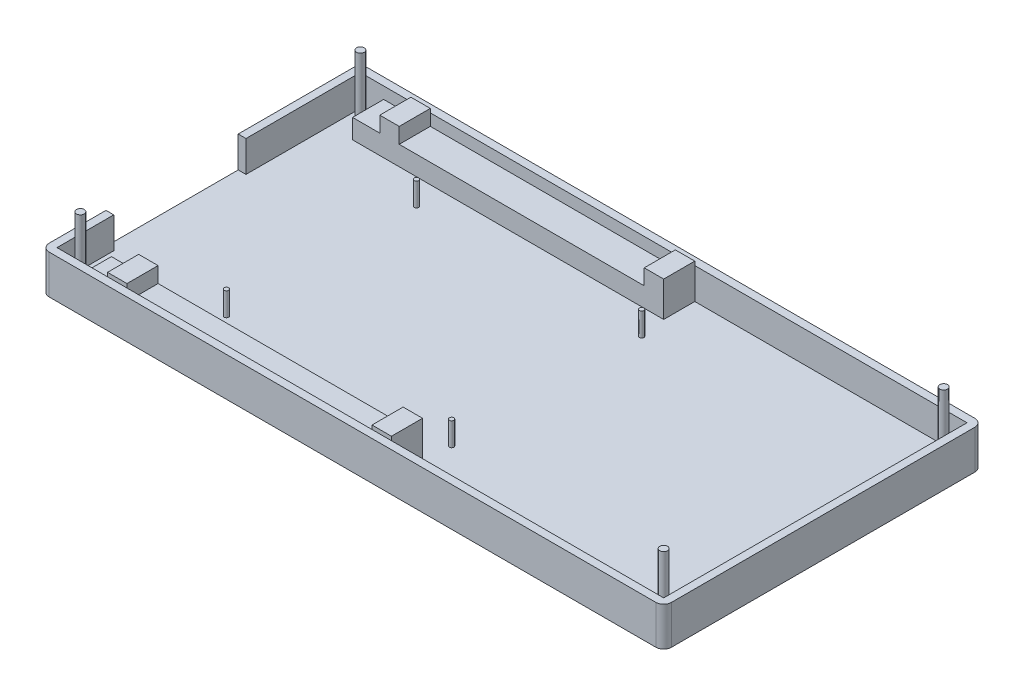
SolidWorks part; units mm, degrees
ref_plane "Front Plane" through (0, 0, 0) normal (0, 0, 1) x (1, 0, 0)
ref_plane "Top Plane" through (0, 0, 0) normal (0, 1, 0) x (1, 0, 0)
ref_plane "Right Plane" through (0, 0, 0) normal (1, 0, 0) x (0, 0, -1)
sketch "Sketch1" plane through (0, 0, 0) normal (0, 1, 0) x (1, 0, 0)
  line L1 (-80, -41) -> (80, -41)
  line L2 (-80, -41) -> (-80, 41)
  line L3 (-80, 41) -> (80, 41)
  line L4 (80, -41) -> (80, 41)
  line L5 (-80, -41) -> (80, 41) construction
  line L6 (-80, 41) -> (80, -41) construction
  point P0 (0, 0)
  dimension "D1" = 160
  dimension "D2" = 82
extrude "Boss-Extrude1" add sketch "Sketch1" along normal blind 10 contours L1 L4 L3 L2
shell "Shell1" thickness 2 removed face at (0, 10, 0)
sketch "Sketch2" plane through (0, 2, 0) normal (0, 1, 0) x (1, 0, 0)
  line L0 (-78, 39) -> (78, 39) construction
  line L1 (-78, -39) -> (-78, 39) construction
  line L2 (0, 39) -> (0, -41) construction
  line L3 (-78, 39) -> (78, 39) construction
  line L4 (-80, -41) -> (80, -41) construction
  line L5 (-80, 0) -> (80, 0) construction
  line L6 (-80, -41) -> (-80, 41) construction
  line L7 (80, -41) -> (80, 41) construction
  circle A0 centre (-75, 36) radius 1
  circle A1 centre (75, 36) radius 1
  circle A2 centre (75, -36) radius 1
  circle A3 centre (-75, -36) radius 1
  dimension "D1" = 3
  dimension "D2" = 3
  dimension "D3" = 2
extrude "Boss-Extrude2" add sketch "Sketch2" along normal blind 16 contours A0 | A3 | A2 | A1
fillet "Fillet1" radius 2 1 edges at (-80, 5, 41)
fillet "Fillet2" radius 2 1 edges at (-80, 5, -41)
fillet "Fillet3" radius 2 1 edges at (80, 5, -41)
fillet "Fillet4" radius 2 1 edges at (80, 5, 41)
sketch "Sketch7" plane through (0, 2, 0) normal (0, 1, 0) x (1, 0, 0)
  line L0 (-49, 24.45) -> (-49, -24.43)
  line L1 (-78, 39) -> (78, 39) construction
  line L2 (-20.05, 24.45) -> (-20.05, -24.43) construction
  line L3 (-49, 0.01) -> (-52.9634, 0.01) construction
  line L4 (-49, 24.45) -> (8.9, 24.45)
  line L5 (8.9, 24.45) -> (8.9, -24.43)
  line L6 (8.9, -24.43) -> (-49, -24.43)
  line L7 (-78, -39) -> (-78, 39) construction
  circle A0 centre (-49, 24.45) radius 0.575
  circle A1 centre (-49, -24.43) radius 0.575
  circle A2 centre (8.9, -24.43) radius 0.575
  circle A3 centre (8.9, 24.45) radius 0.575
  dimension "D3" = 1.15
  dimension "D1" = 48.88
  dimension "D2" = 14.55
  dimension "D4" = 57.9
  dimension "D5" = 29
extrude "Boss-Extrude3" add sketch "Sketch7" along normal blind 6 contours A2 | A1 | A3 | A0
sketch "Sketch10" plane through (-80, 0, 0) normal (-1, 0, 0) x (0, 0, 1)
  line L0 (24.4, 0) -> (-9.6, 0)
  line L2 (39, 0) -> (-39, 0) construction
  line L3 (-9.6, 0) -> (-9.6, 2)
  line L4 (-9.6, 2) -> (24.4, 2)
  line L5 (-9.6, 2) -> (24.4, 2)
  line L6 (-9.6, 2) -> (-9.6, 10.0297)
  line L7 (24.4, 2) -> (24.4, 10.0297)
  line L8 (-9.6, 10.0297) -> (24.4, 10.0297)
  dimension "D1" = 34
  dimension "D2" = 14.6
  dimension "D3" = 2
extrude "Cut-Extrude1" cut sketch "Sketch10" against normal blind 6 contours L4 L7 L8 L6
sketch "Sketch16" plane through (0, 2, 0) normal (0, 1, 0) x (1, 0, 0)
  line L0 (-49, 24.45) -> (-49, 28.15)
  line L1 (-49, -24.43) -> (-49, -28.13)
  line L2 (8.9, -24.43) -> (8.9, -28.13)
  line L3 (8.9, 24.45) -> (8.9, 28.15)
  line L4 (-78, 39) -> (78, 39) construction
  line L5 (-72, 39) -> (8, 39)
  line L6 (-72, 39) -> (-72, 31)
  line L7 (-72, 31) -> (8, 31)
  line L8 (8, 39) -> (8, 31)
  line L9 (78, 0) -> (-83.4739, 0) construction
  line L10 (78, -39) -> (78, 39) construction
  line L11 (8, -39) -> (8, -31)
  line L12 (-72, -39) -> (8, -39)
  line L13 (-72, -39) -> (-72, -31)
  line L14 (-72, -31) -> (8, -31)
  dimension "D1" = 3.7
  dimension "D2" = 3.7
  dimension "D3" = 8
  dimension "D4" = 80
  dimension "D5" = 6
extrude "Boss-Extrude5" add sketch "Sketch16" along normal blind 5 contours L8 L7 L6 L5 | L14 L11 L12 L13
sketch "Sketch18" plane through (0, 7, 0) normal (0, 1, 0) x (1, 0, 0)
  line L0 (-60, 31) -> (3, 31)
  line L1 (-72, 31) -> (8, 31) construction
  line L2 (-60, 39) -> (-60, 31)
  line L3 (-72, 39) -> (8, 39) construction
  line L4 (-60, 39) -> (-65, 39)
  line L5 (-65, 39) -> (-65, 31)
  line L6 (-72, 31) -> (8, 31) construction
  line L7 (-65, 31) -> (-60, 31)
  line L8 (-28.5, 31) -> (-28.5, 39) construction
  line L9 (8, 31) -> (3, 31)
  line L10 (3, 39) -> (3, 31)
  line L11 (8, 39) -> (8, 31)
  line L12 (3, 39) -> (8, 39)
  line L13 (78, 0) -> (-85.0376, 0) construction
  line L14 (78, -39) -> (78, 39) construction
  line L15 (3, -39) -> (8, -39)
  line L16 (8, -39) -> (8, -31)
  line L17 (8, -31) -> (3, -31)
  line L18 (3, -39) -> (3, -31)
  line L19 (-65, -31) -> (-60, -31)
  line L20 (-65, -39) -> (-65, -31)
  line L21 (-60, -39) -> (-65, -39)
  line L22 (-60, -39) -> (-60, -31)
  dimension "D1" = 63
  dimension "D2" = 5
extrude "Boss-Extrude6" add sketch "Sketch18" along normal blind 4 contours L9 L11 L12 L10 | L7 L5 L4 L2 | L16 L17 L18 L15 | L22 L19 L20 L21
